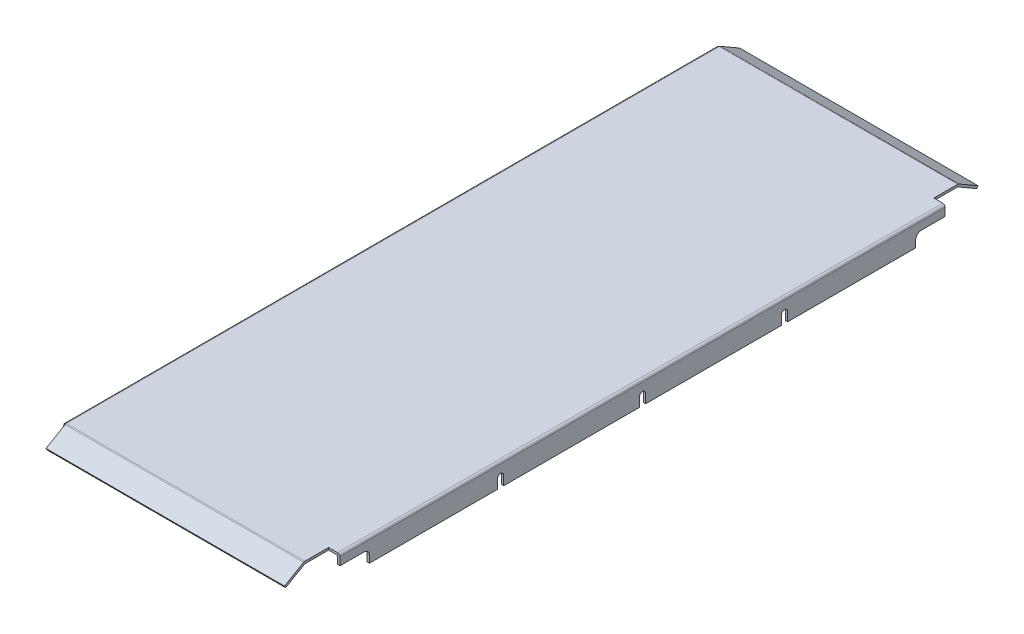
SolidWorks part; units mm, degrees
note: The reader was unsure of these and kept them because the rebuilt part matched: flange length of "Kante-Lasche3", "Kante-Lasche4", "Kante-Lasche5".
material "1.4301 (X5CrNi18-10)"
ref_plane "Vorne" through (0, 0, 0) normal (0, 0, 1) x (1, 0, 0)
ref_plane "Oben" through (0, 0, 0) normal (0, 1, 0) x (1, 0, 0)
ref_plane "Rechts" through (0, 0, 0) normal (1, 0, 0) x (0, 0, -1)
sketch "Skizze9" plane through (0, 0, 0) normal (0, 1, 0) x (1, 0, 0)
  line L1 (-110, 287.5) -> (110, 287.5)
  line L2 (-110, 287.5) -> (-110, -287.5)
  line L3 (-110, -287.5) -> (110, -287.5)
  line L4 (110, 287.5) -> (110, -287.5)
  line L5 (-110, 287.5) -> (110, -287.5) construction
  line L6 (-110, -287.5) -> (110, 287.5) construction
  point P0 (0, 0)
  dimension "D1" = 575
  dimension "D2" = 220
sheet metal parameters "Blech3" thickness 2 parameters "D1"=0.01
base flange "Basis-Blech2" sketch "Skizze9" thickness 2 reverse thickness direction no parameters "D1"=0.01
edge flange "Kante-Lasche3" sketch "Skizze62" flange angle 90 flange length 20 flange position material inside bend radius 0.1 thickness 2 relief rectangular parameters "D6"=10, "D8"=1
sketch "Skizze62" plane through (110, -2, 0) normal (1, 0, 0) x (0, 0, 1)
  line L0 (287.5, 0) -> (-287.5, 0) construction
  line L1 (287.5, 0) -> (-287.5, 0)
  line L2 (0, 0) -> (0, 18) construction
  line L3 (-287.5, 7) -> (-287.5, 0)
  line L4 (287.5, -2) -> (-287.5, -2) construction
  line L5 (-287.5, 7) -> (-245.5, 7)
  line L6 (-240.5, 12) -> (-240.5, 18)
  line L23 (-127.7, 18) -> (-240.5, 18)
  line L24 (-127.7, 10) -> (-127.7, 18)
  line L25 (-122.3, 10) -> (-122.3, 18)
  line L26 (-2.7, 18) -> (-122.3, 18)
  line L27 (-2.7, 10) -> (-2.7, 18)
  line L28 (2.7, 10) -> (2.7, 18)
  line L29 (122.3, 18) -> (2.7, 18)
  line L30 (122.3, 10) -> (122.3, 18)
  line L31 (127.7, 10) -> (127.7, 18)
  line L32 (240.5, 18) -> (127.7, 18)
  line L33 (240.5, 12) -> (240.5, 18)
  line L34 (287.5, 7) -> (245.5, 7)
  line L35 (287.5, 0) -> (287.5, 7)
  arc A0 (-245.5, 7) -> (-240.5, 12) centre (-245.5, 12) ccw
  arc A6 (-127.7, 10) -> (-122.3, 10) centre (-125, 10) ccw
  arc A7 (-2.7, 10) -> (2.7, 10) centre (0, 10) ccw
  arc A8 (122.3, 10) -> (127.7, 10) centre (125, 10) ccw
  arc A9 (240.5, 12) -> (245.5, 7) centre (245.5, 12) ccw
  dimension "D2" = 5
  dimension "D5" = 10.7
  dimension "D6" = 250
  dimension "D1" = 11
  dimension "D3" = 47
  dimension "D4" = 5.4
  dimension "D7" = 20
bend "Kantenbiegung6" bend radius 0.1 bend angle 90 parameters "D5"=10
edge flange "Kante-Lasche4" sketch "Skizze69" flange profiles "Skizze69", "Skizze70" flange angle 150 flange length 20 flange position material outside bend radius 0.01 thickness 2 relief none parameters "D6"=10, "D8"=1
sketch "Skizze69" plane through (0, -2, -287.5) normal (0, -0.866, 0.5) x (-1, 0, 0)
  line L1 (110, 0) -> (-107.9, 0) construction
  line L2 (-107.9, 0) -> (-107.9, 19.4641)
  line L3 (-107.9, 19.4641) -> (110, 19.4641)
  line L4 (110, 19.4641) -> (110, 0)
  line L5 (110, 0) -> (-107.9, 0)
sketch "Skizze70" plane through (0, -2, 287.5) normal (0, -0.866, -0.5) x (1, 0, 0)
  line L0 (107.9, 0) -> (-110, 0) construction
  line L1 (107.9, 0) -> (-110, 0)
  line L2 (107.9, 0) -> (107.9, 19.4641)
  line L3 (107.9, 19.4641) -> (-110, 19.4641)
  line L4 (-110, 19.4641) -> (-110, 0)
bend "Kantenbiegung8" bend radius 0.01 bend angle 30 parameters "D5"=11
bend "Kantenbiegung9" bend radius 0.01 bend angle 30 parameters "D5"=12
sketch "Skizze43" plane through (0, 0, 0) normal (0, 1, 0) x (1, 0, 0)
  line L2 (110, 287.5) -> (110, -287.5) construction
  line L4 (100, 308.4973) -> (110, 308.4973)
  line L5 (100, 308.4973) -> (100, 266.4973)
  line L6 (100, 266.4973) -> (110, 266.4973)
  line L7 (110, 308.4973) -> (110, 266.4973)
  line L8 (100, 308.4973) -> (110, 266.4973) construction
  line L9 (100, 266.4973) -> (110, 308.4973) construction
  line L10 (100, -308.4973) -> (110, -266.4973) construction
  line L11 (100, -266.4973) -> (110, -308.4973) construction
  line L12 (110, -266.4973) -> (110, -308.4973)
  line L13 (100, -308.4973) -> (110, -308.4973)
  line L14 (100, -266.4973) -> (100, -308.4973)
  line L15 (100, -266.4973) -> (110, -266.4973)
  line L17 (-110, -287.4973) -> (107.9, -287.4973) construction
  line L18 (107.9, 287.4973) -> (-110, 287.4973) construction
  point P5 (105, 287.4973)
  point P18 (105, -287.4973)
  dimension "D1" = 42
  dimension "D2" = 10
extrude "Schnitt-Linear austragen4" cut sketch "Skizze43" against normal through all normal cut yes
edge flange "Kante-Lasche5" sketch "Skizze73" flange angle 100 flange length 7 flange position bend outside bend radius 0.1 thickness 2 relief rectangular parameters "D6"=10
sketch "Skizze73" plane through (-110, -2, 0) normal (0.9848, -0.1736, 0) x (0, 0, 1)
  line L1 (287.4973, 0) -> (-287.4973, 0) construction
  line L2 (-287.4973, 0) -> (-287.4973, 7)
  line L3 (-287.4973, 7) -> (287.4973, 7)
  line L4 (287.4973, 7) -> (287.4973, 0)
  line L5 (287.4973, 0) -> (-287.4973, 0)
bend "Kantenbiegung10" bend radius 0.1 bend angle 80 parameters "D5"=13
flat pattern "Abwicklung3" [suppressed]
sketch "Biegung-Linien3" plane through (0, -2, 0) normal (0, -1, 0) x (1, 0, 0)
  line L0 (-110.2793, -287.4973) -> (-110.2793, 287.4973) construction
  line L1 (-110, 287.7617) -> (100, 287.7617) construction
  line L2 (100, -287.7617) -> (-110, -287.7617) construction
  line L3 (108.2142, 266.4973) -> (108.2142, -266.4973) construction
  line L4 (-110.2793, -287.4973) -> (-110.2793, 287.4973) construction
  line L5 (-110, 287.7617) -> (100, 287.7617) construction
  line L6 (100, -287.7617) -> (-110, -287.7617) construction
  line L7 (108.2142, 266.4973) -> (108.2142, -266.4973) construction
sketch3d "Rahmen3" [suppressed]
  line L0 (-227.4746, -594.9876, 0) -> (-227.4746, 19.9876, 0) construction
  line L1 (16.4283, -594.9876, 0) -> (16.4283, 19.9876, 0) construction
  line L2 (-227.4746, -594.9876, 0) -> (16.4283, -594.9876, 0) construction
  line L3 (-227.4746, 19.9876, 0) -> (16.4283, 19.9876, 0) construction
bend of the flat pattern "Abwickeln-<Kantenbiegung6>1"
bend of the flat pattern "Abwickeln-<Kantenbiegung8>1"
bend of the flat pattern "Abwickeln-<Kantenbiegung9>1"
bend of the flat pattern "Abwickeln-<Kantenbiegung10>1"
